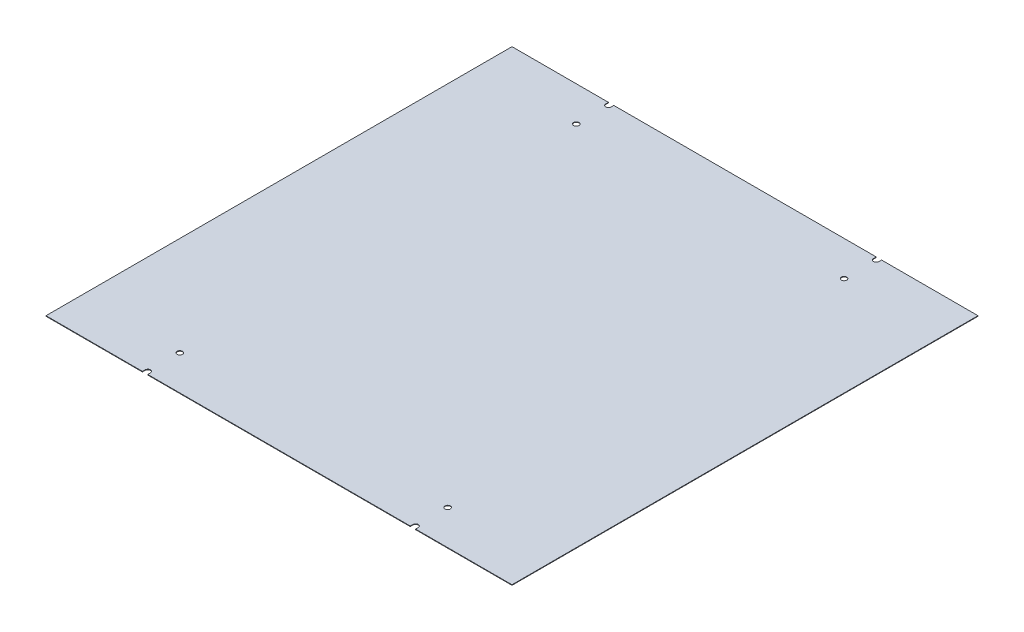
SolidWorks part; units mm, degrees
ref_plane "Front Plane" through (0, 0, 0) normal (0, 0, 1) x (1, 0, 0)
ref_plane "Top Plane" through (0, 0, 0) normal (0, 1, 0) x (1, 0, 0)
ref_plane "Right Plane" through (0, 0, 0) normal (1, 0, 0) x (0, 0, -1)
sketch "Sketch1" plane through (0, 0, 0) normal (0, 1, 0) x (1, 0, 0)
  line L0 (-490, 870) -> (490, 870)
  line L1 (-870, 870) -> (-510, 870)
  line L2 (-870, 870) -> (-870, -870)
  line L3 (-870, -870) -> (-510, -870)
  line L4 (870, 870) -> (870, -870)
  line L5 (490, 850) -> (510, 850)
  line L6 (500, 870) -> (500, 740) construction
  line L7 (-510, 850) -> (-490, 850)
  line L8 (-490, 870) -> (490, 870)
  line L9 (510, -870) -> (870, -870)
  line L11 (510, 870) -> (870, 870)
  line L13 (510, 870) -> (870, 870)
  line L14 (-870, -870) -> (-510, -870)
  line L15 (-500, 870) -> (-500, 740) construction
  line L16 (510, -870) -> (870, -870)
  line L17 (-870, 870) -> (-510, 870)
  line L18 (490, 870) -> (490, 850)
  line L19 (-510, 870) -> (-510, 850)
  line L20 (510, 870) -> (510, 850)
  line L21 (-490, 870) -> (-490, 850)
  line L22 (510, -850) -> (510, -870)
  line L24 (-490, -870) -> (490, -870)
  line L25 (-490, -870) -> (490, -870)
  line L26 (490, -850) -> (490, -870)
  line L28 (-510, -850) -> (-510, -870)
  line L31 (500, -740) -> (500, -870) construction
  line L32 (-490, -850) -> (-490, -870)
  line L33 (500, 870) -> (500, -870) construction
  line L34 (-500, -740) -> (-500, -870) construction
  line L35 (-500, 870) -> (-500, -870) construction
  line L36 (-510, -850) -> (-490, -850)
  line L38 (490, -850) -> (510, -850)
  circle A0 centre (-500, -740) radius 10
  circle A1 centre (500, -740) radius 10
  circle A2 centre (500, 740) radius 10
  circle A3 centre (-500, 740) radius 10
  point P0 (0, 0)
  point P14 (0, 0)
  point P15 (0, 0)
  dimension "D5" = 130
  dimension "D1" = 1740
  dimension "D2" = 1740
  dimension "D6" = 130
  dimension "D7" = 130
  dimension "D8" = 130
  dimension "D3" = 370
  dimension "D4" = 370
extrude "Boss-Extrude1" add sketch "Sketch1" along normal blind 2 contours L26 L38 L22 L9 L4 L11 L20 L5 L18 L0 L21 L7 L19 L1 L2 L3 L28 L36 L32 L24 A3 A2 A1 A0 region at (0, 0, 0)
fillet "Fillet1" radius 10 8 edges at (490, 1, 850) (510, 1, 850) (-510, 1, 850) (-490, 1, 850) (510, 1, -850) (490, 1, -850) (-510, 1, -850) (-490, 1, -850)
